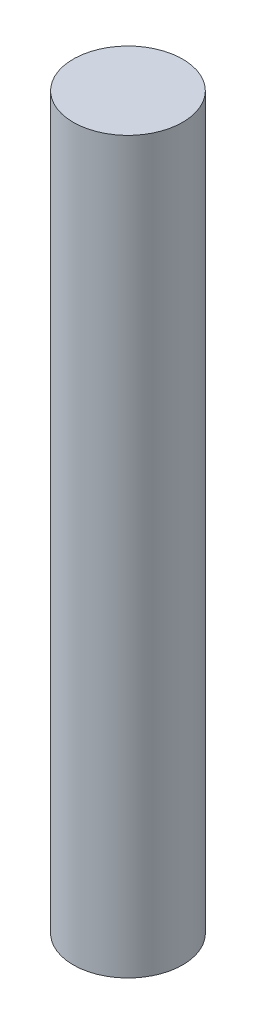
SolidWorks part; units mm, degrees
material "PS Średni/wysoki przepływ"
ref_plane "Płaszczyzna przednia" through (0, 0, 0) normal (0, 0, 1) x (1, 0, 0)
ref_plane "Płaszczyzna górna" through (0, 0, 0) normal (0, 1, 0) x (1, 0, 0)
ref_plane "Płaszczyzna prawa" through (0, 0, 0) normal (1, 0, 0) x (0, 0, -1)
other "Środek masy(COM)"
sketch "Szkic1" plane through (0, 0, 0) normal (0, 1, 0) x (1, 0, 0)
  circle A0 centre (0, 0) radius 3
extrude "Dodanie-wyciągnięcie1" add sketch "Szkic1" along normal blind 40
ref_axis "Oś1" through (0, 40, 0) along (0, -1, 0)
sketch "Szkic2" plane through (0, 40, 0) normal (0, 1, 0) x (1, 0, 0)
  point P0 (0, 0)
ref_point "Punkt1"
sketch "Szkic4" plane through (0, 0, 0) normal (0, -1, 0) x (1, 0, 0)
  point P0 (0, 0)
